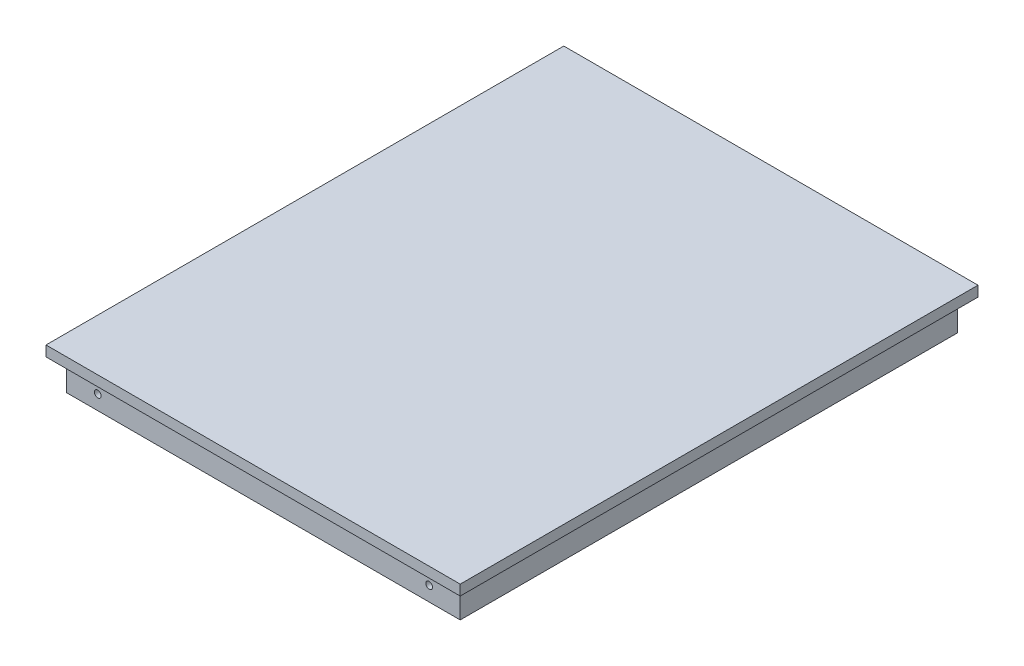
SolidWorks part; units mm, degrees
ref_plane "Front Plane" through (0, 0, 0) normal (0, 0, 1) x (1, 0, 0)
ref_plane "Top Plane" through (0, 0, 0) normal (0, 1, 0) x (1, 0, 0)
ref_plane "Right Plane" through (0, 0, 0) normal (1, 0, 0) x (0, 0, -1)
sketch "Sketch1" plane through (0, 0, 0) normal (0, 1, 0) x (1, 0, 0)
  line L0 (-95, 120) -> (95, 120)
  line L1 (95, 120) -> (95, -120)
  line L2 (95, -120) -> (-95, -120)
  line L3 (-95, -120) -> (-95, 120)
  line L4 (-95, 120) -> (95, 120)
  line L5 (-95, 120) -> (95, -120) construction
  line L6 (-90, 115) -> (90, 115)
  line L7 (90, 115) -> (90, -115)
  line L8 (90, -115) -> (-90, -115)
  line L9 (-90, -115) -> (-90, 115)
  line L10 (-90, 115) -> (90, 115)
  line L11 (-95, 115) -> (95, 115) construction
  line L12 (-95, 115) -> (95, 115) construction
  line L13 (-90, -115) -> (-90, 120) construction
  line L14 (90, 120) -> (90, -115) construction
  line L15 (95, 120) -> (-95, -120) construction
  line L16 (-100, 125) -> (100, 125)
  line L17 (100, 125) -> (100, -125)
  line L18 (100, -125) -> (-100, -125)
  line L19 (-100, -125) -> (-100, 125)
  point P4 (0, 0)
  dimension "D1" = 190
  dimension "D2" = 240
  dimension "D4" = 5
  dimension "D5" = 5
  dimension "D6" = 5
  dimension "D7" = 5
  dimension "D3" = 5
extrude "Boss-Extrude1" add sketch "Sketch1" along normal blind 5 contours L3 L2 L1 L0 L8 L9 L6 L7 | L19 L18 L17 L16 L2 L3 L0 L1 | L9 L8 L7 L6 region at (0, 0, -116.939) region at (0, 0, 0) region at (0, 0, -121.7984)
extrude "Boss-Extrude2" add sketch "Sketch1<3>" against normal blind 15 contours L3 L2 L1 L0 L8 L9 L6 L7 region at (0, 0, -116.939)
sketch "Sketch1<3>" plane through (0, 0, 0) normal (0, 1, 0) x (1, 0, 0) same geometry as "Sketch1"
sketch "Sketch2" plane through (0, 0, 0) normal (0, 0, 1) x (1, 0, 0)
  line L0 (0, 0) -> (-80, 0) construction
  line L2 (0, 0) -> (0, -6.4593) construction
  line L4 (-80, -8) -> (-80, 0) construction
  circle A0 centre (-80, -8) radius 1.625
  circle A1 centre (80, -8) radius 1.625 construction
  point P4 (0, 0)
  dimension "D1" = 3.25
  dimension "D2" = 80
  dimension "D3" = 8
extrude "Cut-Extrude1" cut sketch "Sketch2" along normal through all both and the other way through all
mirror "Mirror1" about plane through (0, 0, 0) normal (1, 0, 0) of "Cut-Extrude1"
